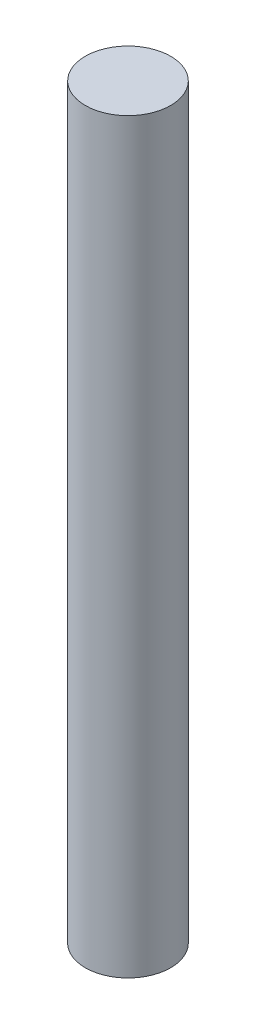
SolidWorks part; units mm, degrees
ref_plane "Alzado" through (0, 0, 0) normal (0, 0, 1) x (1, 0, 0)
ref_plane "Planta" through (0, 0, 0) normal (0, 1, 0) x (1, 0, 0)
ref_plane "Vista lateral" through (0, 0, 0) normal (1, 0, 0) x (0, 0, -1)
sketch "Croquis1" plane through (0, 0, 0) normal (0, 1, 0) x (1, 0, 0)
  circle A0 centre (0, 0) radius 4
  dimension "D1" = 8
extrude "Saliente-Extruir1" add sketch "Croquis1" along normal blind 70
